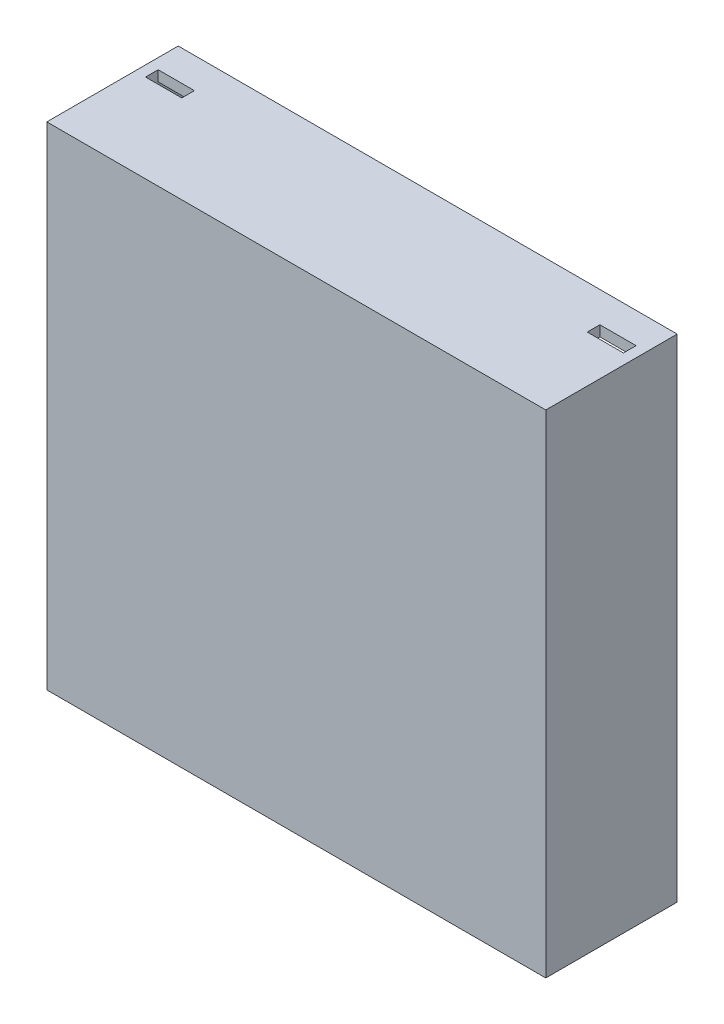
SolidWorks part; units mm, degrees
ref_plane "Front Plane" through (0, 0, 0) normal (0, 0, 1) x (1, 0, 0)
ref_plane "Top Plane" through (0, 0, 0) normal (0, 1, 0) x (1, 0, 0)
ref_plane "Right Plane" through (0, 0, 0) normal (1, 0, 0) x (0, 0, -1)
sketch "Sketch1" plane through (0, 0, 0) normal (0, 0, 1) x (1, 0, 0)
  line L0 (10.75, -9.75) -> (-121.1, -9.75) construction
  line L1 (10.75, 60.25) -> (-60.25, 60.25)
  line L2 (10.75, 60.25) -> (10.75, -9.75)
  line L3 (10.75, -9.75) -> (-60.25, -9.75)
  line L4 (-60.25, 60.25) -> (-60.25, -9.75)
  line L5 (9.25, 58.75) -> (-58.75, 58.75)
  line L6 (-58.75, 58.75) -> (-58.75, -8.25)
  line L7 (9.25, -8.25) -> (-58.75, -8.25)
  line L8 (9.25, 58.75) -> (9.25, -8.25)
  dimension "D1" = 71
  dimension "D2" = 1.5
extrude "Boss-Extrude1" add sketch "Sketch1" along normal blind 17.2
extrude "Boss-Extrude2" add sketch "Sketch1<2>" along normal blind 1.5 from surface contours L4 L3 L2 L1 starting at face at (-24.75, 25.25, 17.2)
sketch "Sketch1<2>" plane through (0, 0, 0) normal (0, 0, 1) x (1, 0, 0) same geometry as "Sketch1"
ref_plane "Plane1" through (0, 25.25, 0) normal (0, 1, 0) x (1, 0, 0)
ref_plane "Plane2" through (-24.75, 0, 0) normal (1, 0, 0) x (0, 0, -1)
ref_plane "Plane3" through (0, 0, 20.975) normal (0, 0, 1) x (1, 0, 0)
sketch "Sketch5" plane through (0, 0, 18.7) normal (0, 0, 1) x (1, 0, 0)
  line L0 (10.75, 60.25) -> (10.75, -9.75) construction
  line L1 (-19, 25.25) -> (-25.25, 25.25) construction
  line L2 (-19, 25.25) -> (-12.75, 25.25) construction
  line L3 (-37.75, 37.75) -> (-12.75, 37.75)
  line L4 (-37.75, 37.75) -> (-37.75, 12.75) construction
  line L5 (-37.75, 12.75) -> (-12.75, 12.75) construction
  line L6 (-12.75, 37.75) -> (-12.75, 12.75) construction
  line L7 (-37.75, 37.75) -> (-12.75, 12.75) construction
  line L8 (-37.75, 12.75) -> (-12.75, 37.75) construction
  line L9 (-37.75, 25.25) -> (-60.25, 25.25) construction
  line L11 (-25.25, 37.75) -> (-25.25, 60.25) construction
  line L12 (10.75, 60.25) -> (-60.25, 60.25) construction
  circle A0 centre (-19, 25.25) radius 0.75
  point P4 (10.75, 25.25)
  point P7 (-25.25, 25.25)
  dimension "D1" = 1.5
  dimension "D3" = 25
sketch "Sketch6" plane through (0, 60.25, 0) normal (0, 1, 0) x (1, 0, 0)
  line L4 (9.25, -17.2) -> (9.25, 0) construction
  line L5 (9.25, -17.2) -> (9.25, 0) construction
  line L8 (4.1, -6.15) -> (9.4, -6.15)
  line L9 (9.4, -6.15) -> (9.4, -4.35)
  line L10 (4.1, -4.35) -> (4.1, -6.15)
  line L11 (9.4, -4.35) -> (4.1, -4.35)
  line L12 (4.1, -6.15) -> (9.25, -6.15)
  line L13 (9.25, -6.15) -> (9.25, -4.35)
  line L14 (4.1, -4.35) -> (4.1, -6.15)
  line L15 (9.25, -4.35) -> (4.1, -4.35)
  dimension "D1" = 0.15
extrude "Cut-Extrude1" cut sketch "Sketch6" against normal up to next
mirror "Mirror1" about plane through (-24.75, 0, 0) normal (1, 0, 0) of "Cut-Extrude1"
mirror "Mirror2" about plane through (0, 25.25, 0) normal (0, 1, 0) of "Mirror1", "Cut-Extrude1"
ref_axis "Axis1" through (-24.75, 25.25, -36.2629) along (0, 0, 1)
sketch "Sketch7" plane through (-60.25, 0, 0) normal (-1, 0, 0) x (0, 0, 1)
  line L8 (11.7, 12.125) -> (11.7, 33.775)
  line L9 (1.78, 12.125) -> (11.7, 12.125)
  line L10 (1.78, 33.775) -> (1.78, 12.125)
  line L11 (11.7, 33.775) -> (1.78, 33.775)
  line L12 (11.7, 12.125) -> (11.7, 33.775)
  line L13 (1.78, 12.125) -> (11.7, 12.125)
  line L14 (1.78, 33.775) -> (1.78, 12.125)
  line L15 (11.7, 33.775) -> (1.78, 33.775)
  dimension "D1" = 1
extrude "Cut-Extrude2" cut sketch "Sketch7" against normal up to next
sketch "Sketch8" plane through (0, 0, 17.2) normal (0, 0, -1) x (-1, 0, 0)
  line L0 (53.75, 13.125) -> (53.75, -0.875) construction
  line L1 (53.75, -0.875) -> (-4.25, -0.875) construction
  line L2 (53.75, 0.625) -> (53.75, -0.875)
  line L3 (53.75, -0.875) -> (52.25, -0.875)
  line L5 (53.75, -0.875) -> (52.25, -0.875)
  line L6 (53.75, -0.875) -> (53.75, 0.625)
  line L7 (53.75, 0.625) -> (52.25, 0.625)
  line L8 (52.25, -0.875) -> (52.25, 0.625)
  circle A0 centre (-1.95, 1.075) radius 0.65 construction
  circle A1 centre (-2.3, 49.625) radius 0.65 construction
  circle A2 centre (51.65, 49.525) radius 0.65 construction
  circle A3 centre (-1.95, 1.075) radius 0.65 construction
  circle A4 centre (-2.3, 49.625) radius 0.65 construction
  circle A5 centre (51.65, 49.525) radius 0.65 construction
  circle A6 centre (-2.3, 49.625) radius 2.15
  circle A7 centre (51.65, 49.525) radius 2.15
  circle A8 centre (-1.95, 1.075) radius 2.15
  circle A9 centre (51.65, 49.525) radius 0.4
  circle A10 centre (-2.3, 49.625) radius 0.4
  circle A11 centre (-1.95, 1.075) radius 0.4
  dimension "D3" = 1.5
  dimension "D1" = 1.5
  dimension "D2" = 0.25
extrude "Boss-Extrude6" add sketch "Sketch8" along normal up to surface (5.7 mm away) contours A7 A9 | A6 A10 | A8 A11 | L8 L3 L2 L7 region at (-53, -0.125, 17.2) region at (4.3892, 49.625, 17.2) region at (-49.5608, 49.525, 17.2) region at (4.0392, 1.075, 17.2)
equation "\"D1@Boss-Extrude1\"=14.2+3"
